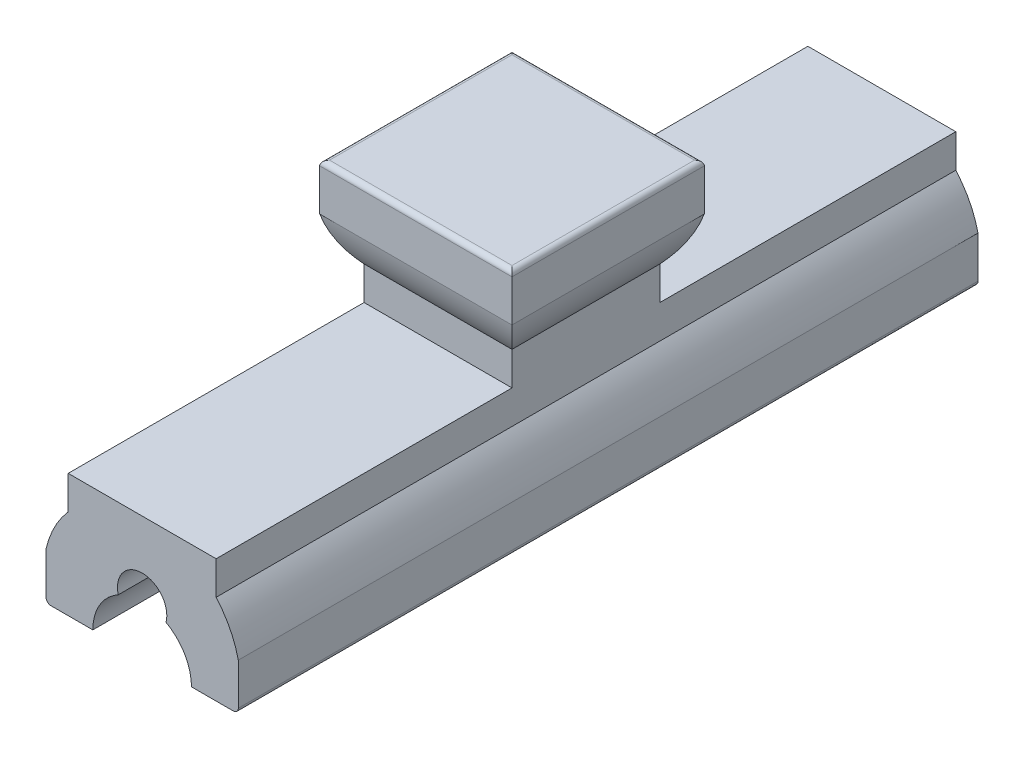
SolidWorks part; units mm, degrees
ref_plane "前视基准面" through (0, 0, 0) normal (0, 0, 1) x (1, 0, 0)
ref_plane "上视基准面" through (0, 0, 0) normal (0, 1, 0) x (1, 0, 0)
ref_plane "右视基准面" through (0, 0, 0) normal (1, 0, 0) x (0, 0, -1)
sketch "草图2" plane through (0, 0, 0) normal (0, 0, 1) x (1, 0, 0)
  line L0 (-1.95, -2.5) -> (-1, -2.5)
  line L1 (-1.5, 0) -> (1.5, 0)
  line L2 (-1.5, 0) -> (-1.5, -0.6771)
  line L3 (1, -2.5) -> (1.95, -2.5)
  line L4 (1.5, 0) -> (1.5, -0.6771)
  line L5 (-1.95, -2.5) -> (-1.95, -1.5556)
  line L6 (1.95, -2.5) -> (1.95, -1.5556)
  arc A0 (1.95, -1.5556) -> (1.5, -0.6771) centre (0, -2) ccw
  arc A1 (-1.5, -0.6771) -> (-1.95, -1.5556) centre (0, -2) ccw
  arc A2 (1, -2.5) -> (0.4841, -1.625) centre (0, -2.5) ccw
  arc A3 (0.4841, -1.625) -> (-0.4841, -1.625) centre (0, -1.5) ccw
  arc A4 (-0.4841, -1.625) -> (-1, -2.5) centre (0, -2.5) ccw
extrude "凸台-拉伸2" add sketch "草图2" along normal blind 7.5 and the other way blind 7.5
sketch "草图3" plane through (0, 0, 0) normal (0, 1, 0) x (-1, 0, 0)
  line L0 (1.5, -7.5) -> (1.5, 7.5) construction
  line L1 (1.5, 1.5) -> (-1.5, 1.5)
  line L2 (1.5, 1.5) -> (1.5, -1.5)
  line L3 (1.5, -1.5) -> (-1.5, -1.5)
  line L4 (-1.5, 1.5) -> (-1.5, -1.5)
  line L5 (-1.5, -7.5) -> (-1.5, 7.5) construction
extrude "凸台-拉伸3" add sketch "草图3" along normal blind 1
sketch "草图4" plane through (0, 0, 0) normal (0, 0, 1) x (1, 0, 0)
  line L0 (-1.5, 1) -> (1.5, 1)
  line L1 (-1.95, 2.5) -> (1.95, 2.5)
  line L2 (-1.95, 2.5) -> (-1.95, 1.5556)
  line L3 (1.95, 2.5) -> (1.95, 1.5556)
  line L5 (-1.5, 1) -> (-1.5, 0) construction
  line L6 (-1.5, 0.6771) -> (1.5, 0.6771)
  arc A0 (-1.95, 1.5556) -> (-1.5, 0.6771) centre (0, 2) ccw
  arc A1 (1.5, 0.6771) -> (1.95, 1.5556) centre (0, 2) ccw
extrude "凸台-拉伸4" add sketch "草图4" along normal blind 2 and the other way blind 2 contours L6 A1 L3 L1 L2 A0 region at (0, 1.6187, 0)
sketch "草图5" plane through (0, 0, 0) normal (1, 0, 0) x (0, 0, -1)
  line L0 (1.95, 2.5) -> (2, 2.5)
  line L1 (-1.95, 2.5) -> (-1.95, 1.5556)
  line L2 (1.95, 2.5) -> (1.95, 1.5556)
  line L4 (-1.95, 2.5) -> (-2, 2.5)
  line L5 (-2, 2.5) -> (-2, 0.6771)
  line L6 (-2, 0.6771) -> (-1.5, 0.6771)
  line L7 (2, 2.5) -> (2, 0.6771)
  line L8 (2, 0.6771) -> (1.5, 0.6771)
  arc A0 (-1.95, 1.5556) -> (-1.5, 0.6771) centre (0, 2) ccw
  arc A1 (1.5, 0.6771) -> (1.95, 1.5556) centre (0, 2) ccw
extrude "切除-拉伸1" cut sketch "草图5" against normal up to next and the other way up to next
fillet "圆角1" radius 0.1 6 edges at (-1.95, 2.5, 0) (0, 2.5, -1.95) (1.95, 2.5, 0) (0, 2.5, 1.95) (-1.95, -2.5, 0) (1.95, -2.5, 0)
